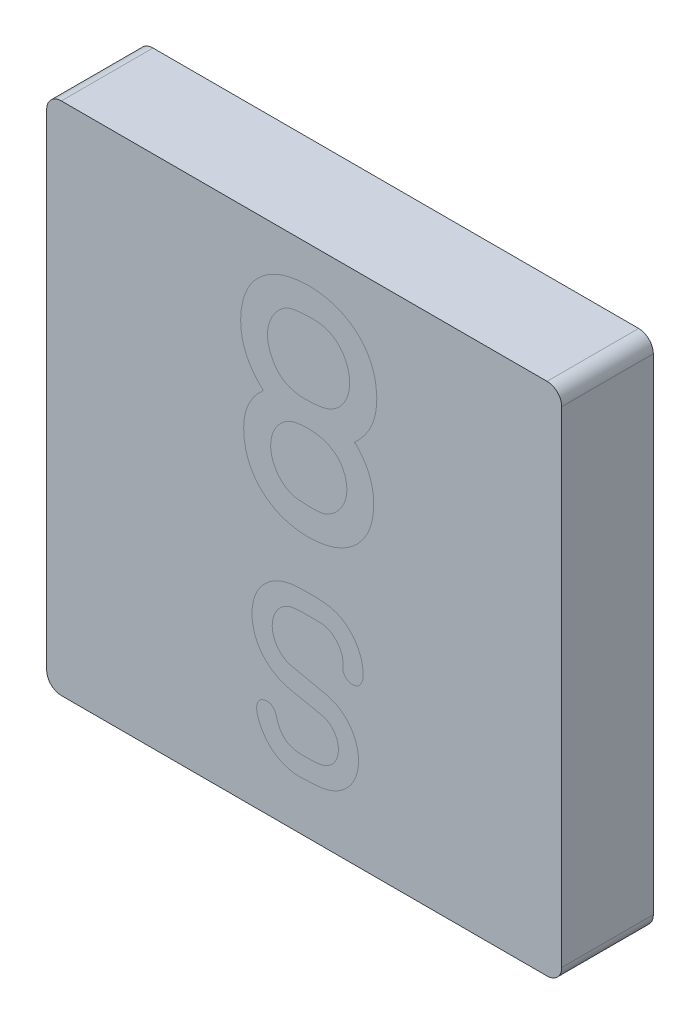
SolidWorks part; units mm, degrees
material "Nylon 101"
ref_plane "Front Plane" through (0, 0, 0) normal (0, 0, 1) x (1, 0, 0)
ref_plane "Top Plane" through (0, 0, 0) normal (0, 1, 0) x (1, 0, 0)
ref_plane "Right Plane" through (0, 0, 0) normal (1, 0, 0) x (0, 0, -1)
sketch "Sketch1" plane through (0, 0, 0) normal (0, 0, 1) x (1, 0, 0)
  line L0 (4.207, 4.715) -> (-4.207, 4.715) construction
  line L1 (4.715, -4.207) -> (4.715, 4.207) construction
  line L2 (-4.207, -4.715) -> (4.207, -4.715) construction
  line L3 (-4.715, 4.207) -> (-4.715, -4.207) construction
  line L4 (4.207, 4.715) -> (-4.207, 4.715) construction
  line L5 (4.715, -4.207) -> (4.715, 4.207) construction
  line L6 (-4.207, -4.715) -> (4.207, -4.715) construction
  line L7 (-4.715, 4.207) -> (-4.715, -4.207) construction
  line L8 (4.207, 4.461) -> (-4.207, 4.461)
  line L9 (-4.461, 4.207) -> (-4.461, -4.207)
  line L10 (-4.207, -4.461) -> (4.207, -4.461)
  line L11 (4.461, -4.207) -> (4.461, 4.207)
  arc A0 (4.715, 4.207) -> (4.207, 4.715) centre (4.207, 4.207) ccw construction
  arc A1 (4.207, -4.715) -> (4.715, -4.207) centre (4.207, -4.207) ccw construction
  arc A2 (-4.715, -4.207) -> (-4.207, -4.715) centre (-4.207, -4.207) ccw construction
  arc A3 (-4.207, 4.715) -> (-4.715, 4.207) centre (-4.207, 4.207) ccw construction
  arc A4 (4.715, 4.207) -> (4.207, 4.715) centre (4.207, 4.207) ccw construction
  arc A5 (4.207, -4.715) -> (4.715, -4.207) centre (4.207, -4.207) ccw construction
  arc A6 (-4.715, -4.207) -> (-4.207, -4.715) centre (-4.207, -4.207) ccw construction
  arc A7 (-4.207, 4.715) -> (-4.715, 4.207) centre (-4.207, 4.207) ccw construction
  arc A8 (-4.207, 4.461) -> (-4.461, 4.207) centre (-4.207, 4.207) ccw
  arc A9 (-4.461, -4.207) -> (-4.207, -4.461) centre (-4.207, -4.207) ccw
  arc A10 (4.207, -4.461) -> (4.461, -4.207) centre (4.207, -4.207) ccw
  arc A11 (4.461, 4.207) -> (4.207, 4.461) centre (4.207, 4.207) ccw
  dimension "D1" = 0.254
extrude "Boss-Extrude1" add sketch "Sketch1" along normal blind 1.5875
sketch "Sketch2" plane through (0, 0, 1.5875) normal (0, 0, 1) x (1, 0, 0)
  line L0 (4.461, 3.8355) -> (-4.461, 3.8355) construction
  line L1 (4.461, -4.207) -> (4.461, 4.207) construction
  line L2 (-4.461, 4.207) -> (-4.461, -4.207) construction
  text T0 "8" font "GordonURWMed" height in points 16
sketch "Sketch4" plane through (0, 0, 1.5875) normal (0, 0, 1) x (1, 0, 0)
  line L0 (4.461, -0.7785) -> (-4.461, -0.7785) construction
  line L1 (4.461, -4.207) -> (4.461, 4.207) construction
  line L2 (-4.461, 4.207) -> (-4.461, -4.207) construction
  text T0 "S" font "GordonURWMed" height in points 12
wrap "Direction" sketch "Sketch4" wrap type scribe source sketch "Sketch4" face at (0, 0, 1.5875)
split line "Number"
sketch "Sketch5" [suppressed] plane through (0, 0, 1.5875) normal (0, 0, 1) x (1, 0, 0)
  line L0 (4.461, 0) -> (-4.461, 0) construction
  line L1 (4.461, -4.207) -> (4.461, 4.207) construction
  line L2 (-4.461, 4.207) -> (-4.461, -4.207) construction
  line L3 (4.461, 1.651) -> (-4.461, 1.651) construction
  text T0 "CLR" font "GordonURWMed" height in points 14
  dimension "D1" = 1.651
wrap "CLR" [suppressed] sketch "Sketch5" source sketch "Sketch5"
sketch "Sketch6" [suppressed] plane through (0, 0, 1.5875) normal (0, 0, 1) x (1, 0, 0)
  line L0 (4.461, 0) -> (-4.461, 0) construction
  line L4 (4.461, 1.651) -> (-4.461, 1.651) construction
  text T0 "ENT" font "GordonURWCon" height in points 16
  dimension "D1" = 1.651
wrap "ENT" [suppressed] sketch "Sketch6" source sketch "Sketch6"
sketch "Sketch8" [suppressed] plane through (0, 0, 1.5875) normal (0, 0, 1) x (1, 0, 0)
  line L0 (4.461, 3.302) -> (-4.461, 3.302) construction
  line L3 (4.461, 0) -> (-4.461, 0) construction
  line L4 (4.461, -0.508) -> (-4.461, -0.508) construction
  text T0 "EM" font "GordonURWCon" height in points 14
  text T1 "CON" font "GordonURWCon" height in points 14
  point P13 (0, 0)
  dimension "D1" = 3.302
  dimension "D2" = 0.508
wrap "EMCON" [suppressed] sketch "Sketch8" source sketch "Sketch8"
sketch "Sketch9" [suppressed] plane through (0, 0, 0) normal (0, 0, 1) x (1, 0, 0)
  line L0 (4.461, 3.302) -> (-4.461, 3.302) construction
  line L3 (4.461, 0) -> (-4.461, 0) construction
  line L4 (4.461, -0.508) -> (-4.461, -0.508) construction
  text T0 "ON" font "GordonURWCon" height in points 14
  text T1 "OFF" font "GordonURWCon" height in points 14
  point P13 (0, 0)
  dimension "D1" = 3.302
  dimension "D2" = 0.508
wrap "ON-OFF" [suppressed] sketch "Sketch9" source sketch "Sketch9" thickness 0.0762 parameters "D1"=0.0762
sketch "Sketch10" [suppressed] plane through (0, 0, 0) normal (0, 0, 1) x (1, 0, 0)
  line L0 (4.461, 0) -> (-4.461, 0) construction
  line L4 (4.461, 1.651) -> (-4.461, 1.651) construction
  text T0 "IFF" font "GordonURWCon" height in points 16
  dimension "D1" = 1.651
wrap "LEGEND" [suppressed] sketch "Sketch10" source sketch "Sketch10" thickness 0.0762 parameters "D1"=0.0762
sketch "Sketch11" plane through (0, 0, 1.5875) normal (0, 0, 1) x (1, 0, 0)
  spline S0 degree 3 poles (0.4333, 2.1341) (0.15, 2.1032) (-0.1198, 2.088) (-0.4121, 2.1993) (-0.5959, 2.4579) (-0.6685, 2.7897) (-0.5423, 3.1163) (-0.3233, 3.3286) (-0.0755, 3.3609) (0.1283, 3.3738) (0.3391, 3.3596) (0.5236, 3.2792) (0.6786, 3.1258) (0.7786, 2.9088) (0.8035, 2.6123) (0.682, 2.313) (0.4333, 2.1341) (0.15, 2.1032) (-0.1198, 2.088) knots -0.201217 -0.119698 -0.046549 0 0.077824 0.141317 0.20865 0.291476 0.367822 0.445307 0.489891 0.538926 0.589041 0.636005 0.676198 0.739165 0.798783 0.880302 0.953451 1 1.077824 1.141317 1.20865 only from (0.1949, 2.1094) to (0.1949, 2.1094)
split line "Split Line1"
